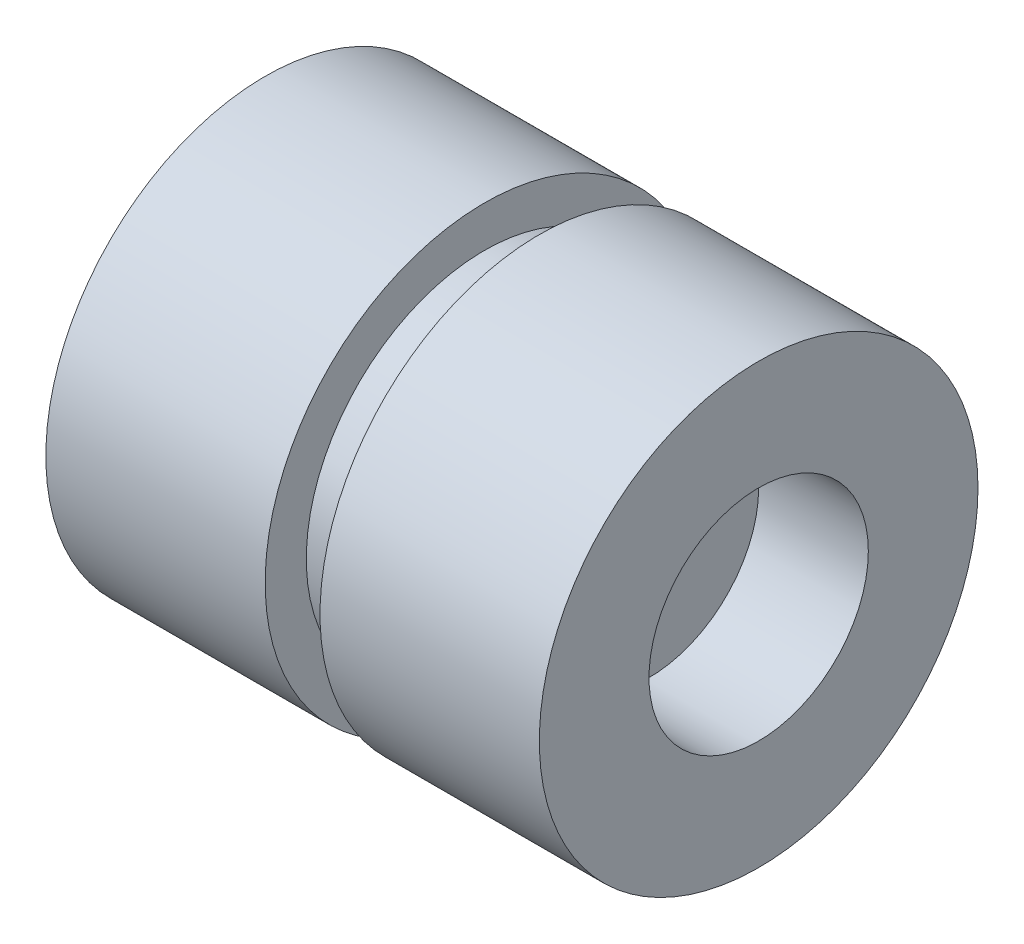
SolidWorks part; units mm, degrees
ref_plane "Front Plane" through (0, 0, 0) normal (0, 0, 1) x (1, 0, 0)
ref_plane "Top Plane" through (0, 0, 0) normal (0, 1, 0) x (1, 0, 0)
ref_plane "Right Plane" through (0, 0, 0) normal (1, 0, 0) x (0, 0, -1)
sketch "Sketch1" plane through (0, 0, 0) normal (0, 0, 1) x (1, 0, 0)
  line L0 (141.0056, 0) -> (-256.8486, 0) construction
  line L2 (0, 101.6) -> (101.6, 101.6)
  line L3 (101.6, 101.6) -> (101.6, 0)
  line L4 (101.6, 0) -> (0, 0)
  line L5 (0, 82.55) -> (-25.4, 82.55)
  line L6 (-25.4, 82.55) -> (-25.4, 101.6)
  line L7 (-25.4, 101.6) -> (-127, 101.6)
  line L8 (-127, 101.6) -> (-127, 0)
  line L9 (-127, 0) -> (-25.4, 0)
  line L18 (0, 82.55) -> (0, 101.6)
  line L19 (-25.4, 0) -> (0, 0)
  dimension "D1" = 101.6
  dimension "D2" = 101.6
  dimension "D3" = 101.6
  dimension "D4" = 101.6
  dimension "D5" = 25.4
  dimension "D6" = 19.05
revolve "Revolve2" add sketch "Sketch1" angle 360 about L0
sketch "Sketch8" plane through (101.6, 0, 0) normal (1, 0, 0) x (0, 0, -1)
  circle A0 centre (0, 0) radius 50.8
  dimension "D1" = 101.6
extrude "Cut-Extrude3" cut sketch "Sketch8" against normal blind 50.8
sketch "Sketch9" plane through (-127, 0, 0) normal (-1, 0, 0) x (0, 0, 1)
  circle A0 centre (0, 0) radius 50.8
  dimension "D1" = 101.6
ref_plane "Plane1" through (-57.15, 0, 0) normal (1, 0, 0) x (0, 0, -1)
sketch "Sketch10" plane through (-57.15, 0, 0) normal (1, 0, 0) x (0, 0, -1)
  circle A0 centre (0, 0) radius 12.7
  dimension "D1" = 25.4
loft "Cut-Loft1" cut profiles "Sketch9", "Sketch10" connector at (-127, 1.6595, -50.7729) connector at (-57.15, -3.879, -12.0931)
